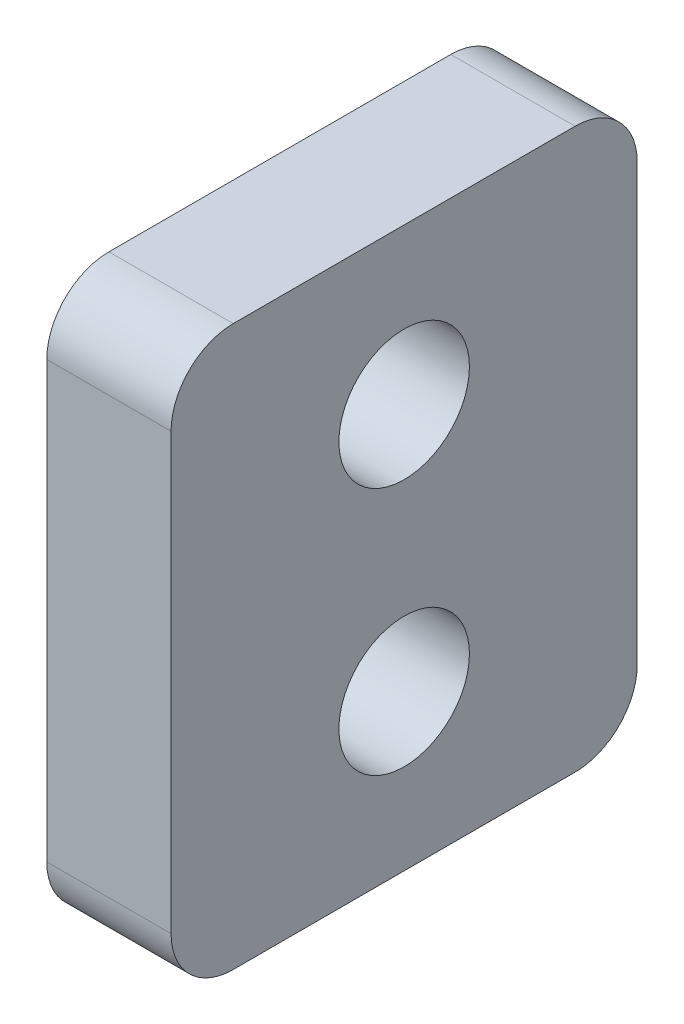
SolidWorks part; units mm, degrees
ref_plane "Front Plane" through (0, 0, 0) normal (0, 0, 1) x (1, 0, 0)
ref_plane "Top Plane" through (0, 0, 0) normal (0, 1, 0) x (1, 0, 0)
ref_plane "Right Plane" through (0, 0, 0) normal (1, 0, 0) x (0, 0, -1)
sketch "Sketch4" plane through (0, 0, 0) normal (1, 0, 0) x (0, 0, -1)
  line L0 (-7.5, 0) -> (7.5, 0) construction
  line L1 (-7.5, -9) -> (7.5, -9)
  line L2 (-7.5, -9) -> (-7.5, 9)
  line L3 (-7.5, 9) -> (7.5, 9)
  line L4 (7.5, -9) -> (7.5, 9)
  line L5 (-7.5, -9) -> (7.5, 9) construction
  line L6 (-7.5, 9) -> (7.5, -9) construction
  line L7 (0, 4) -> (0, -4) construction
  circle A0 centre (0, 4) radius 2.1
  circle A1 centre (0, -4) radius 2.1
  point P0 (0, 0)
  point P12 (-1.0017, 4)
  dimension "D3" = 8
  dimension "D4" = 4.2
  dimension "D1" = 18
  dimension "D2" = 15
extrude "Boss-Extrude1" add sketch "Sketch4" along normal blind 4
fillet "Fillet1" radius 2 4 edges at (2, -9, -7.5) (2, -9, 7.5) (2, 9, -7.5) (2, 9, 7.5)
